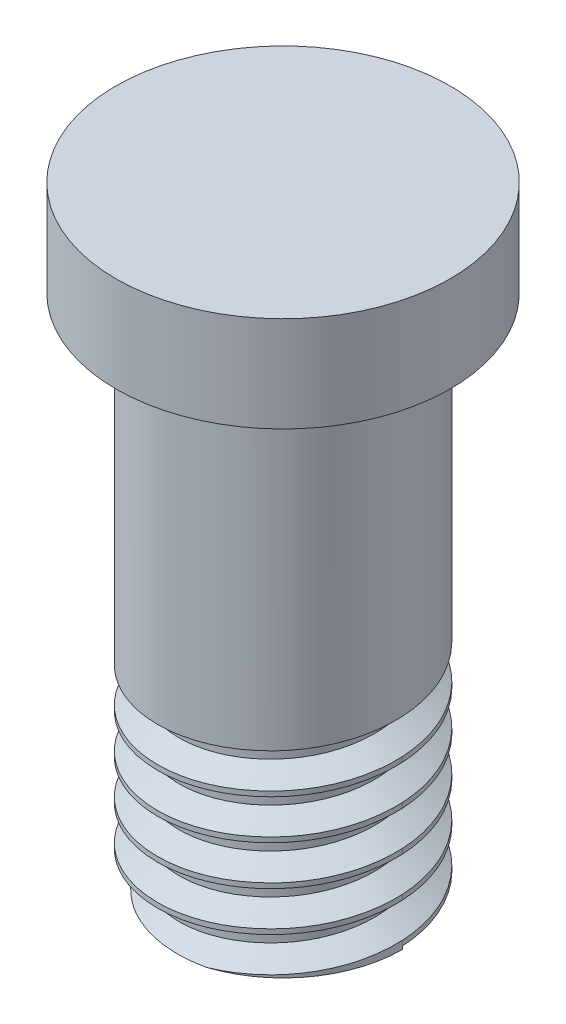
SolidWorks part; units mm, degrees
ref_plane "Front Plane" through (0, 0, 0) normal (0, 0, 1) x (1, 0, 0)
ref_plane "Top Plane" through (0, 0, 0) normal (0, 1, 0) x (1, 0, 0)
ref_plane "Right Plane" through (0, 0, 0) normal (1, 0, 0) x (0, 0, -1)
sketch "Sketch1" plane through (0, 0, 0) normal (0, 1, 0) x (1, 0, 0)
  circle A0 centre (0, 0) radius 3.75
  dimension "D1" = 7.5
extrude "Boss-Extrude1" add sketch "Sketch1" along normal blind 16
sketch "Sketch2" plane through (0, 16, 0) normal (0, 1, 0) x (1, 0, 0)
  circle A0 centre (0, 0) radius 5.25
  circle A1 centre (0, 0) radius 3.75 construction
  dimension "D1" = 1.5
extrude "Boss-Extrude2" add sketch "Sketch2" along normal blind 3
thread "Thread1" pitch 1.25 method cut profile "Thread Profile1" start angle 0, offset 1, length 7, pitch 1.25, diameter 7.5
ref_plane "Plane1" through (3.75, -1, 0) normal (0, 0, 1) x (1, 0, 0)
sketch "Thread Profile1" plane through (3.75, -1, 0) normal (0, 0, 1) x (1, 0, 0)
  line L0 (0, 0) -> (0, 1.25) construction
  line L11 (0, 0) -> (0, 1.0937)
  line L12 (0, 1.0937) -> (-0.6766, 0.7031)
  line L13 (-0.6766, 0.7031) -> (-0.6766, 0.3906)
  line L15 (-0.6766, 0.3906) -> (0, 0)
  line L17 (-0.6766, 0.5469) -> (0, 0.5469) construction
  point P2 (0, 0)
  dimension "Pitch" = 1.25
  dimension "Profile_Angle" = 60
  dimension "Profile_Land" = 0.3125
  dimension "Profile_Height" = 0.6766
